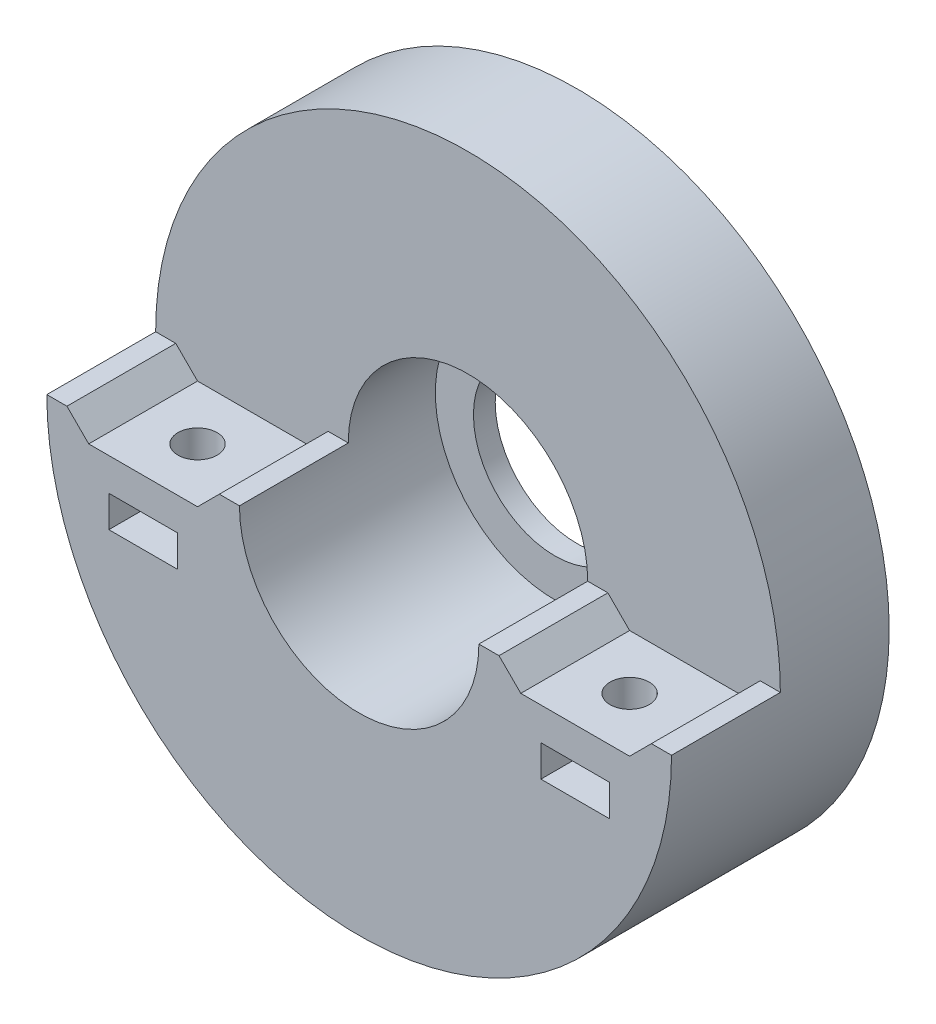
SolidWorks part; units mm, degrees
ref_plane "Plano frontal" through (0, 0, 0) normal (0, 0, 1) x (1, 0, 0)
ref_plane "Plano superior" through (0, 0, 0) normal (0, 1, 0) x (1, 0, 0)
ref_plane "Plano direito" through (0, 0, 0) normal (1, 0, 0) x (0, 0, -1)
sketch "Esboço1" plane through (0, 0, 0) normal (0, 0, 1) x (1, 0, 0)
  circle A2 centre (0, 0) radius 28.7
  dimension "D3" = 57.4
extrude "Ressalto-extrusão1" add sketch "Esboço1" along normal mid plane 10
sketch "Esboço2" plane through (0, 0, 5) normal (0, 0, 1) x (1, 0, 0)
  circle A0 centre (0, 0) radius 11
  dimension "D1" = 22
extrude "Corte-extrusão1" cut sketch "Esboço2" against normal blind 8
sketch "Esboço3" plane through (0, 0, -5) normal (0, 0, -1) x (-1, 0, 0)
  circle A0 centre (0, 0) radius 7.5
  dimension "D1" = 15
extrude "Corte-extrusão2" cut sketch "Esboço3" against normal through all
sketch "Esboço8" plane through (0, 0, 5) normal (0, 0, 1) x (1, 0, 0)
  line L0 (-11, 0) -> (-28.7, 0)
  line L1 (11, 0) -> (28.7, 0)
  arc A0 (-11, 0) -> (11, 0) centre (0, 0) ccw
  circle A1 centre (0, 0) radius 11 construction
  arc A2 (-28.7, 0) -> (28.7, 0) centre (0, 0) ccw
  circle A3 centre (0, 0) radius 28.7 construction
extrude "Ressalto-extrusão4" add sketch "Esboço8" along normal blind 10
sketch "Esboço9" plane through (0, 0, 15) normal (0, 0, 1) x (1, 0, 0)
  line L0 (-11, 0) -> (-28.7, 0) construction
  line L1 (0, -11) -> (0, 11) construction
  line L2 (-11, 0) -> (-28.7, 0) construction
  line L3 (-14.85, 0) -> (-24.85, 0)
  line L4 (-14.85, 0) -> (-14.85, -2)
  line L5 (-14.85, -2) -> (-24.85, -2)
  line L6 (-24.85, 0) -> (-24.85, -2)
  line L7 (24.85, 0) -> (24.85, -2)
  line L8 (14.85, -2) -> (24.85, -2)
  line L9 (14.85, 0) -> (14.85, -2)
  line L10 (14.85, 0) -> (24.85, 0)
  point P7 (-19.85, 0)
  point P10 (-19.85, 0)
  dimension "D1" = 10
  dimension "D2" = 2
extrude "Corte-extrusão5" cut sketch "Esboço9" against normal up to surface (10 mm away) up to face at (0, 9.925, 5)
chamfer "Chanfro1" distance 2 angle 45 4 edges at (24.85, 0, 10) (14.85, 0, 10) (-14.85, 0, 10) (-24.85, 0, 10)
sketch "Esboço10" plane through (0, -2, 0) normal (0, 1, 0) x (1, 0, 0)
  line L0 (-24.85, -15) -> (-14.85, -15) construction
  line L1 (-14.85, -5) -> (-14.85, -15) construction
  line L2 (0, -11) -> (0, 11) construction
  circle A0 centre (-19.85, -10) radius 1.8
  circle A2 centre (19.85, -10) radius 1.8
  point P4 (-19.85, -15)
  point P7 (-14.85, -10)
  dimension "D1" = 3.6
extrude "Corte-extrusão6" cut sketch "Esboço10" against normal blind 10
sketch "Esboço11" plane through (0, -2, 0) normal (0, 1, 0) x (1, 0, 0)
  line L0 (-23, -8.1813) -> (-23, -11.8187)
  line L1 (-23, -11.8187) -> (-19.85, -13.6373) construction
  line L2 (-19.85, -13.6373) -> (-16.7, -11.8187) construction
  line L3 (-16.7, -11.8187) -> (-16.7, -8.1813)
  line L4 (-16.7, -8.1813) -> (-19.85, -6.3627)
  line L5 (-19.85, -6.3627) -> (-23, -8.1813)
  line L6 (-16.7, -11.8187) -> (-16.7, -15)
  line L7 (-24.85, -15) -> (-14.85, -15) construction
  line L8 (-16.7, -15) -> (-23, -15)
  line L9 (-23, -15) -> (-23, -11.8187)
  line L10 (0, -11) -> (0, 11) construction
  line L11 (19.85, -13.6373) -> (16.7, -11.8187) construction
  line L12 (23, -11.8187) -> (19.85, -13.6373) construction
  line L13 (23, -15) -> (23, -11.8187)
  line L14 (16.7, -15) -> (23, -15)
  line L15 (16.7, -11.8187) -> (16.7, -15)
  line L16 (19.85, -6.3627) -> (23, -8.1813)
  line L17 (16.7, -8.1813) -> (19.85, -6.3627)
  line L18 (16.7, -11.8187) -> (16.7, -8.1813)
  line L19 (23, -8.1813) -> (23, -11.8187)
  circle A0 centre (-19.85, -10) radius 3.6373 construction
  circle A1 centre (19.85, -10) radius 3.6373 construction
  dimension "D1" = 6.3
extrude "Corte-extrusão7" cut sketch "Esboço11" against normal blind 2.9 from offset 3 offset against normal yes
